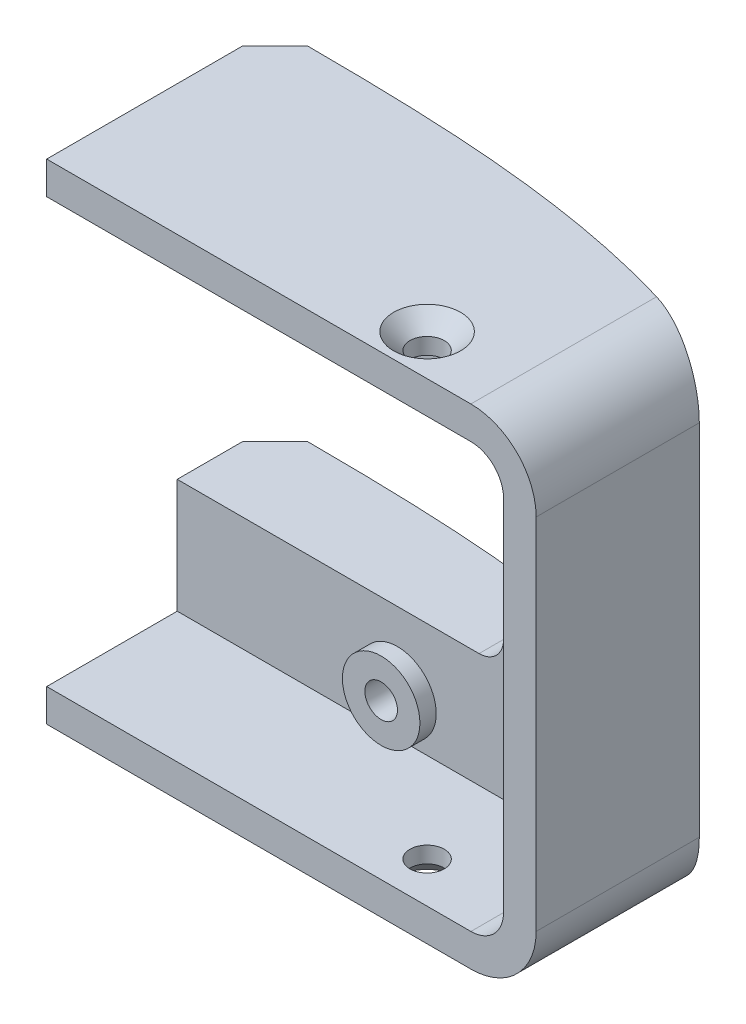
SolidWorks part; units mm, degrees
ref_plane "前视基准面" through (0, 0, 0) normal (0, 0, 1) x (1, 0, 0)
ref_plane "上视基准面" through (0, 0, 0) normal (0, 1, 0) x (1, 0, 0)
ref_plane "右视基准面" through (0, 0, 0) normal (1, 0, 0) x (0, 0, -1)
other "Configuration Table"
sketch "草图2" plane through (0, 0, 0) normal (0, 0, 1) x (1, 0, 0)
  line L1 (18.0576, 5.4113) -> (-11.9424, 5.4113)
  line L2 (18.0576, 5.4113) -> (18.0576, -24.5887)
  line L3 (18.0576, -24.5887) -> (-11.9424, -24.5887)
  line L4 (-11.9424, 5.4113) -> (-11.9424, -24.5887)
  dimension "D1" = 30
  dimension "D2" = 30
extrude "凸台-拉伸1" add sketch "草图2" against normal blind 10
shell "抽壳1" thickness 2
sketch "草图3" plane through (0, 0, 0) normal (0, 0, 1) x (1, 0, 0)
  line L0 (-11.9424, 5.4113) -> (-11.9424, -24.5887) construction
  line L1 (-11.9424, -22.5887) -> (16.0576, -22.5887)
  line L2 (-11.9424, -22.5887) -> (-11.9424, 3.4113)
  line L3 (-11.9424, 3.4113) -> (16.0576, 3.4113)
  line L4 (16.0576, -22.5887) -> (16.0576, 3.4113)
  line L5 (16.0576, -22.5887) -> (16.0576, 3.4113) construction
extrude "切除-拉伸1" cut sketch "草图3" against normal up to next
sketch "草图4" plane through (0, -24.5887, 0) normal (0, -1, 0) x (1, 0, 0)
  line L1 (-11.9424, -10) -> (-11.9424, -14)
  line L2 (-11.9424, -10) -> (18.0576, -10)
  spline S0 degree 3 poles (-11.9424, -14) (-1.4718, -14.0066) (8.4407, -13.8133) (18.0576, -10) knots 0 0 0 0 1 1 1 1
  dimension "D1" = 4
extrude "凸台-拉伸2" add sketch "草图4" against normal up to surface (30 mm away) up to face at (3.0576, 5.4113, -5)
sketch "草图5" plane through (0, 0, 0) normal (0, 0, 1) x (1, 0, 0)
  line L0 (-11.9424, 3.4113) -> (-11.9424, -22.5887) construction
  line L1 (6.5576, -3.5887) -> (-11.9424, -3.5887)
  line L2 (8.0576, -5.0887) -> (8.0576, -14.0887)
  line L3 (6.5576, -15.5887) -> (-11.9424, -15.5887)
  line L4 (-11.9424, -3.5887) -> (-11.9424, -15.5887)
  line L6 (18.0576, -24.5887) -> (18.0576, 5.4113) construction
  arc A1 (8.0576, -14.0887) -> (6.5576, -15.5887) centre (6.5576, -14.0887) cw
  arc A2 (6.5576, -3.5887) -> (8.0576, -5.0887) centre (6.5576, -5.0887) cw
  point P9 (18.0576, -9.5887)
  point P10 (8.0576, -9.5887)
  point P19 (8.0576, -15.5887)
  point P22 (8.0576, -3.5887)
  dimension "D3" = 1.5
  dimension "D1" = 20
  dimension "D2" = 12
extrude "切除-拉伸2" cut sketch "草图5" against normal through all
sketch "草图6" plane through (0, 0, -8) normal (0, 0, 1) x (1, 0, 0)
  circle A0 centre (1.5576, 0.9087) radius 2.375
  circle A1 centre (14.0576, 0.9087) radius 2.375
  circle A2 centre (1.5576, -20.0913) radius 2.375
  circle A3 centre (14.0576, -20.0913) radius 2.375
extrude "凸台-拉伸3" add sketch "草图6" along normal blind 1
sketch "草图7" plane through (0, 0, -7) normal (0, 0, 1) x (1, 0, 0)
  circle A0 centre (1.5576, -20.0913) radius 1
  circle A1 centre (14.0576, -20.0913) radius 1
  circle A2 centre (1.5576, 0.9087) radius 1
  circle A3 centre (14.0576, 0.9087) radius 1
  dimension "D1" = 2
extrude "切除-拉伸3" cut sketch "草图7" against normal blind 3 draft 2
fillet "圆角2" radius 2 6 edges at (16.0576, -21.3722, -7.5) (16.0576, -21.9804, -8) (16.0576, 3.4113, -4) (16.0576, -22.5887, -4) (16.0576, 2.8005, -8) (16.0576, 2.1896, -7.5)
fillet "圆角3" radius 4 2 edges at (18.0576, -24.5887, -5) (18.0576, 5.4113, -5)
sketch "草图8" plane through (0, 5.4113, 0) normal (0, 1, 0) x (1, 0, 0)
  circle A0 centre (8.8741, 2.5) radius 1.05
  dimension "D1" = 2.1
extrude "切除-拉伸4" cut sketch "草图8" against normal through all
chamfer "倒角1" distance 1 angle 45 2 edges at (7.8241, -24.5887, -2.5) (7.8241, 5.4113, -2.5)
chamfer "倒角2" distance 2 angle 45 1 edges at (-11.9424, -20.0887, -14)
